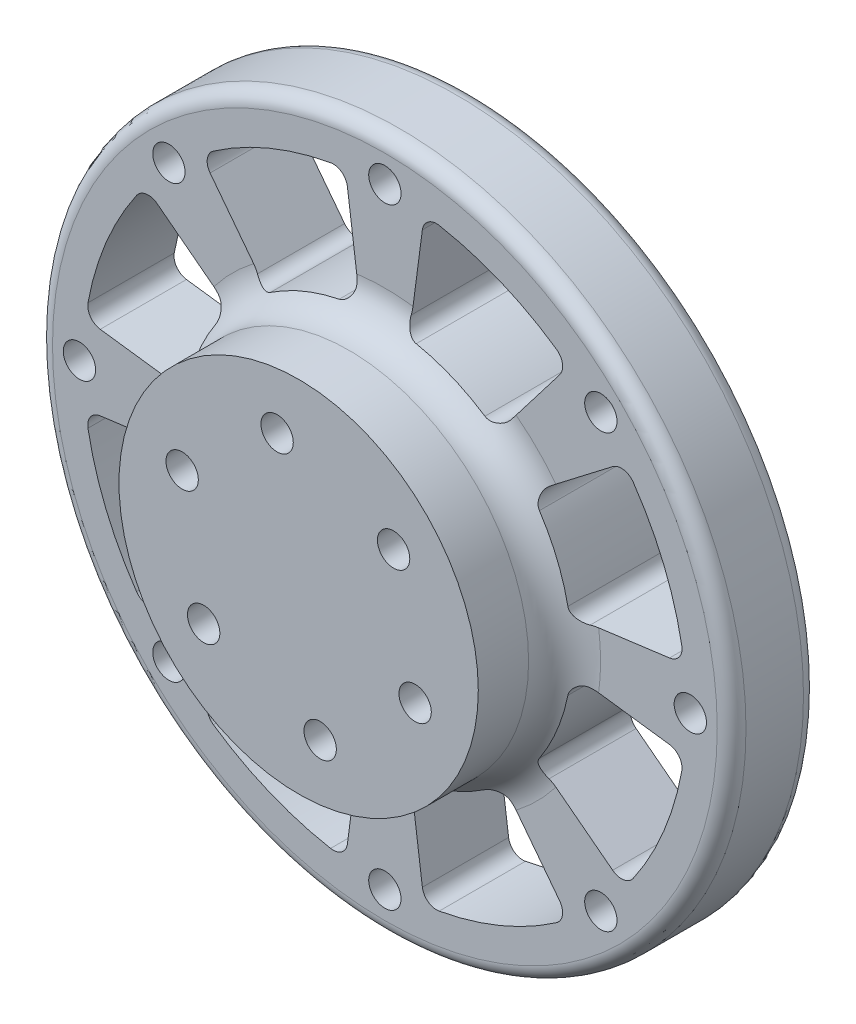
SolidWorks part; units mm, degrees
ref_plane "前视基准面" through (0, 0, 0) normal (0, 0, 1) x (1, 0, 0)
ref_plane "上视基准面" through (0, 0, 0) normal (0, 1, 0) x (1, 0, 0)
ref_plane "右视基准面" through (0, 0, 0) normal (1, 0, 0) x (0, 0, -1)
other "Configuration Table"
sketch "草图1" plane through (0, 0, 0) normal (0, 0, 1) x (1, 0, 0)
  circle A0 centre (0, 0) radius 48.25
  circle A1 centre (0, 0) radius 42.5 construction
  circle A2 centre (0, 42.5) radius 2.25
  circle A3 centre (30.052, 30.052) radius 2.25
  circle A4 centre (42.5, 0) radius 2.25
  circle A5 centre (30.052, -30.052) radius 2.25
  circle A6 centre (0, -42.5) radius 2.25
  circle A7 centre (-30.052, -30.052) radius 2.25
  circle A8 centre (-42.5, 0) radius 2.25
  circle A9 centre (-30.052, 30.052) radius 2.25
  point P23 (0, 0)
  dimension "D1" = 96.5
  dimension "D2" = 85
  dimension "D3" = 4.5
  dimension "D4" = 8
extrude "凸台-拉伸1" add sketch "草图1" along normal blind 12
sketch "草图2" plane through (0, 0, 12) normal (0, 0, 1) x (1, 0, 0)
  line L0 (0, 25) -> (0, -25) construction
  line L1 (-4.3412, 24.6202) -> (4.3412, -24.6202)
  circle A0 centre (0, 0) radius 25
  circle A1 centre (0, 0) radius 17.25 construction
  circle A2 centre (-2.9954, 16.9879) radius 2.25
  circle A3 centre (13.2143, 11.0881) radius 2.25
  circle A4 centre (16.2097, -5.8998) radius 2.25
  circle A5 centre (2.9954, -16.9879) radius 2.25
  circle A6 centre (-13.2143, -11.0881) radius 2.25
  circle A7 centre (-16.2097, 5.8998) radius 2.25
  point P19 (0, 0)
  dimension "D1" = 34.5
  dimension "D2" = 4.5
  dimension "D4" = 50
  dimension "D5" = 10
  dimension "D6" = 0
  dimension "D3" = 6
extrude "凸台-拉伸3" add sketch "草图2" along normal blind 12 contours A5 L1 A0 A2 A4 A3 | A5 L1 A2 A0 A7 A6 region at (10.4659, 1.8454, 12) region at (-10.4659, -1.8454, 12)
sketch "草图5" plane through (0, 0, 24) normal (0, 0, 1) x (1, 0, 0)
  circle A0 centre (2.9954, -16.9879) radius 2.25 construction
  circle A1 centre (16.2097, -5.8998) radius 2.25 construction
  circle A2 centre (13.2143, 11.0881) radius 2.25 construction
  circle A3 centre (-2.9954, 16.9879) radius 2.25 construction
  circle A4 centre (-13.2143, -11.0881) radius 2.25 construction
  circle A5 centre (-16.2097, 5.8998) radius 2.25 construction
  circle A6 centre (2.9954, -16.9879) radius 2.25
  circle A7 centre (16.2097, -5.8998) radius 2.25
  circle A8 centre (13.2143, 11.0881) radius 2.25
  circle A9 centre (-2.9954, 16.9879) radius 2.25
  circle A10 centre (-13.2143, -11.0881) radius 2.25
  circle A11 centre (-16.2097, 5.8998) radius 2.25
extrude "切除-拉伸2" cut sketch "草图5" against normal blind 53
fillet "圆角1" radius 5 1 edges at (25, 0, 12)
fillet "圆角2" radius 2 2 edges at (48.25, 0, 12) (48.25, 0, 0)
sketch "草图6" plane through (0, 0, 0) normal (0, 0, -1) x (-1, 0, 0)
  line L0 (0, 0) -> (-5.4821, 41.6407)
  line L1 (0, 42) -> (0, -42) construction
  line L2 (0, 0) -> (-25.568, 33.3208)
  line L3 (0, 0) -> (5.4821, 41.6407)
  line L4 (0, 0) -> (25.568, 33.3208)
  line L5 (0, 0) -> (33.3208, 25.568)
  line L6 (0, 0) -> (41.6407, 5.4821)
  line L7 (0, 0) -> (41.6407, -5.4821)
  line L8 (0, 0) -> (33.3208, -25.568)
  line L9 (0, 0) -> (25.568, -33.3208)
  line L10 (0, 0) -> (5.4821, -41.6407)
  line L11 (0, 0) -> (-5.4821, -41.6407)
  line L12 (0, 0) -> (-25.568, -33.3208)
  line L13 (0, 0) -> (-33.3208, -25.568)
  line L14 (0, 0) -> (-41.6407, -5.4821)
  line L15 (0, 0) -> (-41.6407, 5.4821)
  line L16 (0, 0) -> (-33.3208, 25.568)
  circle A0 centre (0, 0) radius 42
  circle A1 centre (0, 0) radius 27
  point P25 (0, 0)
  dimension "D1" = 84
  dimension "D2" = 54
  dimension "D3" = 30
  dimension "D4" = 7.5
  dimension "D5" = 8
extrude "切除-拉伸3" cut sketch "草图6" against normal blind 53 contours A1 L16 A0 L15 | A1 L0 A0 L2 | A1 L4 A0 L3 | A1 L6 A0 L5 | A1 L8 A0 L7 | A1 L10 A0 L9 | A1 L12 A0 L11 | A1 L14 A0 L13 region at (13.2579, 32.0074, 0) region at (-13.2579, 32.0074, 0) region at (-32.0074, 13.2579, 0) region at (-32.0074, -13.2579, 0) region at (-13.2579, -32.0074, 0) region at (13.2579, -32.0074, 0) region at (32.0074, -13.2579, 0) region at (32.0074, 13.2579, 0)
fillet "圆角3" radius 2 32 edges at (-26.769, 3.5242, 6.5) (-21.4205, 16.4366, 6.5) (-33.3208, 25.568, 6) (-41.6407, 5.4821, 6) (-5.4821, 41.6407, 6) (-25.568, 33.3208, 6) (-3.5242, 26.769, 6.5) (-16.4366, 21.4205, 6.5) (16.4366, 21.4205, 6.5) (3.5242, 26.769, 6.5) (25.568, 33.3208, 6) (5.4821, 41.6407, 6) (41.6407, 5.4821, 6) (33.3208, 25.568, 6) (21.4205, 16.4366, 6.5) (26.769, 3.5242, 6.5) (41.6407, -5.4821, 6) (26.769, -3.5242, 6.5) (21.4205, -16.4366, 6.5) (33.3208, -25.568, 6) (25.568, -33.3208, 6) (5.4821, -41.6407, 6) (16.4366, -21.4205, 6.5) (3.5242, -26.769, 6.5) (-3.5242, -26.769, 6.5) (-16.4366, -21.4205, 6.5) (-5.4821, -41.6407, 6) (-25.568, -33.3208, 6) (-33.3208, -25.568, 6) (-41.6407, -5.4821, 6) (-26.769, -3.5242, 6.5) (-21.4205, -16.4366, 6.5)
